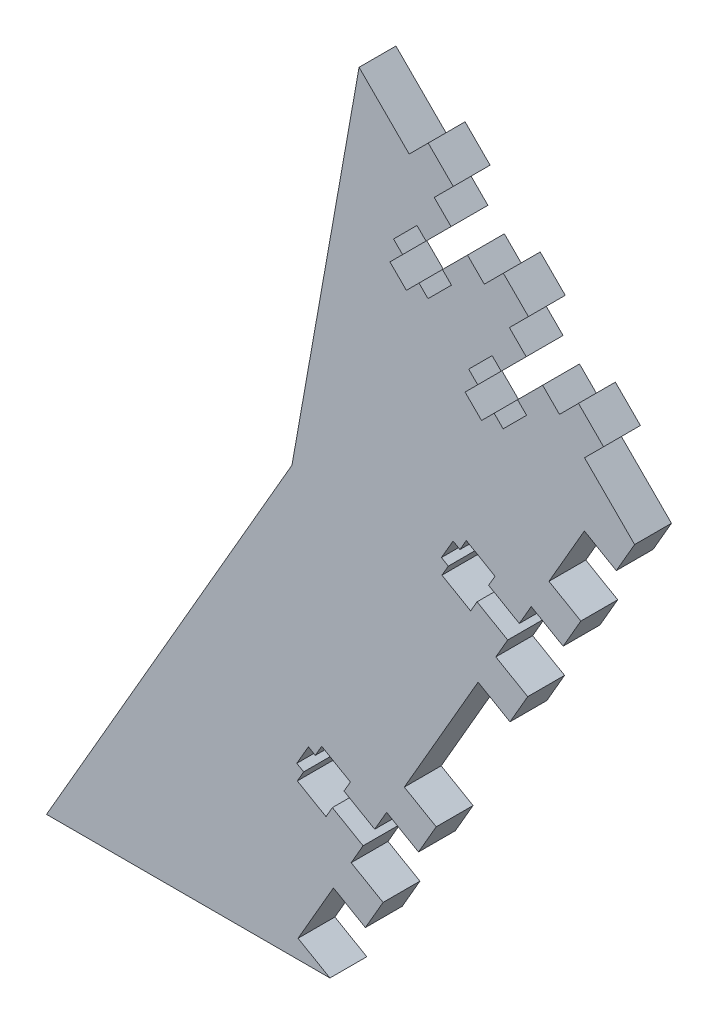
SolidWorks part; units mm, degrees
material "Acrylic (Blue)"
ref_plane "Front Plane" through (0, 0, 0) normal (0, 0, 1) x (1, 0, 0)
ref_plane "Top Plane" through (0, 0, 0) normal (0, 1, 0) x (1, 0, 0)
ref_plane "Right Plane" through (0, 0, 0) normal (1, 0, 0) x (0, 0, -1)
sketch "Sketch1" plane through (0, 0, 0) normal (0, 0, 1) x (1, 0, 0)
  line L0 (0, 0) -> (0, 304.4261) construction
  line L1 (0, 304.4261) -> (215.5261, 88.9)
  line L2 (215.5261, 88.9) -> (164.1997, 0)
  line L3 (164.1997, 0) -> (0, 0)
  line L4 (0, 304.4261) -> (-215.5261, 88.9)
  line L5 (-215.5261, 88.9) -> (-164.1997, 0)
  line L6 (-164.1997, 0) -> (0, 0)
  line L7 (-215.5261, 88.9) -> (215.5261, 88.9) construction
  line L8 (0, 304.4261) -> (3.5921, 308.0182) construction
  line L9 (3.5921, 308.0182) -> (219.1182, 92.4921) construction
  line L10 (219.1182, 92.4921) -> (215.5261, 88.9) construction
  line L11 (3.5921, 308.0182) -> (0, 311.6104) construction
  line L12 (0, 311.6104) -> (-219.1182, 92.4921) construction
  line L13 (-219.1182, 92.4921) -> (-215.5261, 88.9) construction
  line L14 (215.5261, 88.9) -> (219.9256, 86.36) construction
  line L15 (219.9256, 86.36) -> (168.5991, -2.54) construction
  line L16 (168.5991, -2.54) -> (164.1997, 0) construction
  line L17 (164.1997, 0) -> (164.1997, -12.7) construction
  line L18 (164.1997, -12.7) -> (-164.1997, -12.7) construction
  line L19 (-164.1997, -12.7) -> (-164.1997, 0) construction
  line L20 (-164.1997, 0) -> (-168.5991, -2.54) construction
  line L21 (-168.5991, -2.54) -> (-219.9256, 86.36) construction
  line L22 (-219.9256, 86.36) -> (-215.5261, 88.9) construction
  dimension "D1" = 304.8
  dimension "D2" = 120
  dimension "D3" = 88.9
  dimension "D4" = 5.08
  dimension "D5" = 12.7
extrude "Boss-Extrude1" add sketch "Sketch1" along normal blind 6.604
other "Move Face2" face at (107.7631, 196.6631, 3.302) offset 6.35 parameters "D1"=6.35
sketch "Sketch2" plane through (0, 0, 6.604) normal (0, 0, 1) x (1, 0, 0)
  line L1 (113.3997, 0) -> (157.3938, 76.2)
  line L2 (-164.1997, 0) -> (164.1997, 0) construction
  line L3 (157.3938, 76.2) -> (169.4217, 143.9847)
  line L4 (218.8131, 94.5933) -> (4.4901, 308.9163) construction
  line L5 (164.1997, 0) -> (218.8131, 94.5933) construction
  line L7 (169.4217, 143.9847) -> (4.4901, 308.9163)
  line L9 (4.4901, 308.9163) -> (-215.5261, 88.9)
  line L10 (-215.5261, 88.9) -> (-164.1997, 0)
  line L11 (-164.1997, 0) -> (113.3997, 0)
  line B0 (188.424, 103.0706) -> (191.3695, 100.1251) construction
  dimension "D1" = 50.8
  dimension "D2" = 12.7
  dimension "D3" = 76.2
  dimension "D4" = 12.7
sketch_block_instance "NUT_HOLE_2X-1"
sketch_block "NUT_HOLE_2X" parameters "D1"=6.35, "D2"=4.1656, "D3"=25.4, "D4"=4.826, "D5"=8.7376, "D6"=5.9436, "D7"=6.35, "D8"=20.32, "D9"=2
extrude "Cut-Extrude1" cut sketch "Sketch2" against normal through all
sketch "Sketch3" plane through (0, 0, 6.604) normal (0, 0, 1) x (1, 0, 0)
  line L0 (164.1997, 0) -> (218.8131, 94.5933) construction
  line L5 (158.4805, 3.302) -> (209.8069, 92.202)
  line L6 (164.1997, 0) -> (158.4805, 3.302)
  line L7 (215.5261, 88.9) -> (164.1997, 0)
  line L8 (209.8069, 92.202) -> (215.5261, 88.9)
  dimension "D1" = 6.604
  dimension "D2" = 102.6529
extrude "Cut-Extrude2" cut sketch "Sketch3" against normal through all
sketch "Sketch4" plane through (0, 0, 6.604) normal (0, 0, 1) x (1, 0, 0)
  line L0 (218.8131, 94.5933) -> (169.4217, 143.9847) construction
  line L1 (209.8069, 92.202) -> (158.4805, 3.302) construction
  line L2 (215.5261, 88.9) -> (209.8069, 92.202) construction
  point P9 (212.6665, 90.551)
  line B0 (198.1483, 72.0087) -> (192.6491, 75.1837) construction
  line B1 (192.6491, 75.1837) -> (193.7921, 77.1634) construction
  line B2 (193.7921, 77.1634) -> (188.6447, 80.1352) construction
  line B3 (188.6447, 80.1352) -> (187.5017, 78.1555) construction
  line B4 (187.5017, 78.1555) -> (186.2699, 78.8667) construction
  line B5 (186.2699, 78.8667) -> (184.1871, 75.2592) construction
  line B6 (184.1871, 75.2592) -> (185.4189, 74.548) construction
  line B7 (185.4189, 74.548) -> (184.2759, 72.5683) construction
  line B8 (184.2759, 72.5683) -> (189.4233, 69.5965) construction
  line B9 (189.4233, 69.5965) -> (190.5663, 71.5762) construction
  line B10 (190.5663, 71.5762) -> (196.0655, 68.4012) construction
  line B11 (196.0655, 68.4012) -> (193.9319, 64.7057) construction
  line B12 (193.9319, 64.7057) -> (199.6511, 61.4037) construction
  line B13 (199.6511, 61.4037) -> (196.4761, 55.9044) construction
  line B14 (196.4761, 55.9044) -> (190.7569, 59.2064) construction
  line B15 (198.1483, 72.0087) -> (200.2819, 75.7042) construction
  line B16 (200.2819, 75.7042) -> (206.0011, 72.4022) construction
  line B17 (206.0011, 72.4022) -> (209.1761, 77.9015) construction
  line B18 (209.1761, 77.9015) -> (203.4569, 81.2035) construction
  line B19 (196.0655, 68.4012) -> (198.1483, 72.0087) construction
  line B20 (172.2219, 27.1028) -> (166.7226, 30.2778) construction
  line B21 (166.7226, 30.2778) -> (167.8656, 32.2575) construction
  line B22 (167.8656, 32.2575) -> (162.7183, 35.2293) construction
  line B23 (162.7183, 35.2293) -> (161.5753, 33.2496) construction
  line B24 (161.5753, 33.2496) -> (160.3435, 33.9608) construction
  line B25 (160.3435, 33.9608) -> (158.2607, 30.3533) construction
  line B26 (158.2607, 30.3533) -> (159.4925, 29.6421) construction
  line B27 (159.4925, 29.6421) -> (158.3495, 27.6624) construction
  line B28 (158.3495, 27.6624) -> (163.4968, 24.6906) construction
  line B29 (163.4968, 24.6906) -> (164.6398, 26.6703) construction
  line B30 (164.6398, 26.6703) -> (170.1391, 23.4953) construction
  line B31 (170.1391, 23.4953) -> (168.0055, 19.7998) construction
  line B32 (168.0055, 19.7998) -> (173.7247, 16.4978) construction
  line B33 (173.7247, 16.4978) -> (170.5497, 10.9985) construction
  line B34 (170.5497, 10.9985) -> (164.8305, 14.3005) construction
  line B35 (172.2219, 27.1028) -> (174.3555, 30.7983) construction
  line B36 (174.3555, 30.7983) -> (180.0747, 27.4963) construction
  line B37 (180.0747, 27.4963) -> (183.2497, 32.9956) construction
  line B38 (183.2497, 32.9956) -> (177.5305, 36.2976) construction
  line B39 (170.1391, 23.4953) -> (172.2219, 27.1028) construction
  line B40 (185.9095, 127.4969) -> (181.4194, 123.0068) construction
  line B41 (181.4194, 123.0068) -> (179.8029, 124.6232) construction
  line B42 (179.8029, 124.6232) -> (175.6002, 120.4205) construction
  line B43 (175.6002, 120.4205) -> (177.2166, 118.804) construction
  line B44 (177.2166, 118.804) -> (174.9536, 116.541) construction
  line B45 (174.9536, 116.541) -> (177.8991, 113.5955) construction
  line B46 (177.8991, 113.5955) -> (180.1621, 115.8585) construction
  line B47 (180.1621, 115.8585) -> (181.7786, 114.2421) construction
  line B48 (181.7786, 114.2421) -> (185.9813, 118.4448) construction
  line B49 (185.9813, 118.4448) -> (184.3649, 120.0613) construction
  line B50 (184.3649, 120.0613) -> (188.855, 124.5514) construction
  line B51 (188.855, 124.5514) -> (191.8724, 121.534) construction
  line B52 (191.8724, 121.534) -> (195.2849, 124.9465) construction
  line B53 (195.2849, 124.9465) -> (199.775, 120.4564) construction
  line B54 (199.775, 120.4564) -> (196.3625, 117.0439) construction
  line B55 (185.9095, 127.4969) -> (182.8921, 130.5143) construction
  line B56 (182.8921, 130.5143) -> (186.3046, 133.9268) construction
  line B57 (186.3046, 133.9268) -> (181.8145, 138.4169) construction
  line B58 (181.8145, 138.4169) -> (178.402, 135.0044) construction
  line B59 (213.2454, 106.986) -> (209.8329, 103.5735) construction
  line B60 (199.3799, 114.0265) -> (194.8897, 109.5364) construction
  line B61 (194.8897, 109.5364) -> (193.2733, 111.1528) construction
  line B62 (193.2733, 111.1528) -> (189.0705, 106.9501) construction
  line B63 (189.0705, 106.9501) -> (190.687, 105.3336) construction
  line B64 (190.687, 105.3336) -> (188.424, 103.0706) construction
  line B65 (188.424, 103.0706) -> (191.3695, 100.1251) construction
  line B66 (191.3695, 100.1251) -> (193.6325, 102.3881) construction
  line B67 (193.6325, 102.3881) -> (195.249, 100.7717) construction
  line B68 (195.249, 100.7717) -> (199.4517, 104.9744) construction
  line B69 (199.4517, 104.9744) -> (197.8353, 106.5909) construction
  line B70 (197.8353, 106.5909) -> (202.3254, 111.081) construction
  line B71 (202.3254, 111.081) -> (205.3428, 108.0636) construction
  line B72 (205.3428, 108.0636) -> (208.7553, 111.4761) construction
  line B73 (208.7553, 111.4761) -> (213.2454, 106.986) construction
  line B74 (199.3799, 114.0265) -> (196.3625, 117.0439) construction
  line B75 (202.3254, 111.081) -> (199.3799, 114.0265) construction
  dimension "D1" = 12.7
  dimension "D2" = 12.7
  dimension "D3" = 12.7
sketch_block_instance "NUT_HOLE-21"
sketch_block "NUT_HOLE" parameters "D1"=6.35, "D2"=4.1656, "D3"=25.4, "D4"=6.604, "D5"=8.7376, "D6"=5.9436, "D7"=6.35, "D8"=20.32
sketch_block_instance "NUT_HOLE-22"
sketch_block_instance "NUT_HOLE_2X-3"
sketch "Sketch5" plane through (0, 0, 6.604) normal (0, 0, 1) x (1, 0, 0)
  line L0 (185.9095, 127.4969) -> (181.4194, 123.0068) construction
  line L1 (179.8029, 124.6232) -> (175.6002, 120.4205) construction
  line L2 (175.6002, 120.4205) -> (177.2166, 118.804) construction
  line L3 (177.2166, 118.804) -> (174.9536, 116.541) construction
  line L4 (174.9536, 116.541) -> (177.8991, 113.5955) construction
  line L5 (177.8991, 113.5955) -> (180.1621, 115.8585) construction
  line L6 (180.1621, 115.8585) -> (181.7786, 114.2421) construction
  line L7 (181.7786, 114.2421) -> (185.9813, 118.4448) construction
  line L8 (184.3649, 120.0613) -> (188.855, 124.5514) construction
  line L9 (185.9813, 118.4448) -> (184.3649, 120.0613) construction
  line L10 (197.8353, 106.5909) -> (202.3254, 111.081) construction
  line L11 (199.3799, 114.0265) -> (194.8897, 109.5364) construction
  line L12 (194.8897, 109.5364) -> (193.2733, 111.1528) construction
  line L13 (193.2733, 111.1528) -> (189.0705, 106.9501) construction
  line L14 (189.0705, 106.9501) -> (190.687, 105.3336) construction
  line L15 (190.687, 105.3336) -> (188.424, 103.0706) construction
  line L16 (188.424, 103.0706) -> (191.3695, 100.1251) construction
  line L17 (191.3695, 100.1251) -> (193.6325, 102.3881) construction
  line L18 (193.6325, 102.3881) -> (195.249, 100.7717) construction
  line L19 (195.249, 100.7717) -> (199.4517, 104.9744) construction
  line L20 (199.4517, 104.9744) -> (197.8353, 106.5909) construction
  line L21 (185.9095, 127.4969) -> (181.4194, 123.0068)
  line L22 (179.8029, 124.6232) -> (175.6002, 120.4205)
  line L23 (175.6002, 120.4205) -> (177.2166, 118.804)
  line L24 (177.2166, 118.804) -> (174.9536, 116.541)
  line L25 (174.9536, 116.541) -> (177.8991, 113.5955)
  line L26 (177.8991, 113.5955) -> (180.1621, 115.8585)
  line L27 (180.1621, 115.8585) -> (181.7786, 114.2421)
  line L28 (181.7786, 114.2421) -> (185.9813, 118.4448)
  line L29 (184.3649, 120.0613) -> (188.855, 124.5514)
  line L30 (185.9813, 118.4448) -> (184.3649, 120.0613)
  line L31 (197.8353, 106.5909) -> (202.3254, 111.081)
  line L32 (199.3799, 114.0265) -> (194.8897, 109.5364)
  line L33 (194.8897, 109.5364) -> (193.2733, 111.1528)
  line L34 (193.2733, 111.1528) -> (189.0705, 106.9501)
  line L35 (189.0705, 106.9501) -> (190.687, 105.3336)
  line L36 (190.687, 105.3336) -> (188.424, 103.0706)
  line L37 (188.424, 103.0706) -> (191.3695, 100.1251)
  line L38 (191.3695, 100.1251) -> (193.6325, 102.3881)
  line L39 (193.6325, 102.3881) -> (195.249, 100.7717)
  line L40 (195.249, 100.7717) -> (199.4517, 104.9744)
  line L41 (199.4517, 104.9744) -> (197.8353, 106.5909)
  line L42 (181.4194, 123.0068) -> (179.8029, 124.6232) construction
  line L43 (181.4194, 123.0068) -> (179.8029, 124.6232)
  line L44 (198.1483, 72.0087) -> (192.6491, 75.1837) construction
  line L45 (192.6491, 75.1837) -> (193.7921, 77.1634) construction
  line L46 (193.7921, 77.1634) -> (188.6447, 80.1352) construction
  line L47 (188.6447, 80.1352) -> (187.5017, 78.1555) construction
  line L48 (187.5017, 78.1555) -> (186.2699, 78.8667) construction
  line L49 (186.2699, 78.8667) -> (184.1871, 75.2592) construction
  line L50 (184.1871, 75.2592) -> (185.4189, 74.548) construction
  line L51 (185.4189, 74.548) -> (184.2759, 72.5683) construction
  line L52 (184.2759, 72.5683) -> (189.4233, 69.5965) construction
  line L53 (189.4233, 69.5965) -> (190.5663, 71.5762) construction
  line L54 (190.5663, 71.5762) -> (196.0655, 68.4012) construction
  line L55 (172.2219, 27.1028) -> (166.7226, 30.2778) construction
  line L56 (167.8656, 32.2575) -> (162.7183, 35.2293) construction
  line L57 (162.7183, 35.2293) -> (161.5753, 33.2496) construction
  line L58 (161.5753, 33.2496) -> (160.3435, 33.9608) construction
  line L59 (160.3435, 33.9608) -> (158.2607, 30.3533) construction
  line L60 (158.2607, 30.3533) -> (159.4925, 29.6421) construction
  line L61 (159.4925, 29.6421) -> (158.3495, 27.6624) construction
  line L62 (158.3495, 27.6624) -> (163.4968, 24.6906) construction
  line L63 (163.4968, 24.6906) -> (164.6398, 26.6703) construction
  line L64 (164.6398, 26.6703) -> (170.1391, 23.4953) construction
  line L65 (166.7226, 30.2778) -> (167.8656, 32.2575) construction
  line L66 (198.1483, 72.0087) -> (192.6491, 75.1837)
  line L67 (192.6491, 75.1837) -> (193.7921, 77.1634)
  line L68 (193.7921, 77.1634) -> (188.6447, 80.1352)
  line L69 (188.6447, 80.1352) -> (187.5017, 78.1555)
  line L70 (187.5017, 78.1555) -> (186.2699, 78.8667)
  line L71 (186.2699, 78.8667) -> (184.1871, 75.2592)
  line L72 (184.1871, 75.2592) -> (185.4189, 74.548)
  line L73 (185.4189, 74.548) -> (184.2759, 72.5683)
  line L74 (184.2759, 72.5683) -> (189.4233, 69.5965)
  line L75 (189.4233, 69.5965) -> (190.5663, 71.5762)
  line L76 (190.5663, 71.5762) -> (196.0655, 68.4012)
  line L77 (172.2219, 27.1028) -> (166.7226, 30.2778)
  line L78 (167.8656, 32.2575) -> (162.7183, 35.2293)
  line L79 (162.7183, 35.2293) -> (161.5753, 33.2496)
  line L80 (161.5753, 33.2496) -> (160.3435, 33.9608)
  line L81 (160.3435, 33.9608) -> (158.2607, 30.3533)
  line L82 (158.2607, 30.3533) -> (159.4925, 29.6421)
  line L83 (159.4925, 29.6421) -> (158.3495, 27.6624)
  line L84 (158.3495, 27.6624) -> (163.4968, 24.6906)
  line L85 (163.4968, 24.6906) -> (164.6398, 26.6703)
  line L86 (164.6398, 26.6703) -> (170.1391, 23.4953)
  line L87 (166.7226, 30.2778) -> (167.8656, 32.2575)
  line L88 (170.1391, 23.4953) -> (172.2219, 27.1028)
  line L89 (198.1483, 72.0087) -> (196.0655, 68.4012)
  line L90 (185.9095, 127.4969) -> (188.855, 124.5514)
  line L91 (199.3799, 114.0265) -> (202.3254, 111.081)
  point P0 (179.8029, 124.6232)
extrude "Cut-Extrude3" cut sketch "Sketch5" against normal through all
sketch "Sketch6" plane through (0, 0, 6.604) normal (0, 0, 1) x (1, 0, 0)
  line L0 (181.8145, 138.4169) -> (178.402, 135.0044) construction
  line L1 (182.8921, 130.5143) -> (186.3046, 133.9268) construction
  line L2 (186.3046, 133.9268) -> (181.8145, 138.4169) construction
  line L3 (191.8724, 121.534) -> (195.2849, 124.9465) construction
  line L4 (195.2849, 124.9465) -> (199.775, 120.4564) construction
  line L5 (199.775, 120.4564) -> (196.3625, 117.0439) construction
  line L6 (208.7553, 111.4761) -> (213.2454, 106.986) construction
  line L7 (205.3428, 108.0636) -> (208.7553, 111.4761) construction
  line L8 (213.2454, 106.986) -> (209.8329, 103.5735) construction
  line L9 (181.8145, 138.4169) -> (178.402, 135.0044)
  line L10 (182.8921, 130.5143) -> (186.3046, 133.9268)
  line L11 (186.3046, 133.9268) -> (181.8145, 138.4169)
  line L12 (191.8724, 121.534) -> (195.2849, 124.9465)
  line L13 (195.2849, 124.9465) -> (199.775, 120.4564)
  line L14 (199.775, 120.4564) -> (196.3625, 117.0439)
  line L15 (208.7553, 111.4761) -> (213.2454, 106.986)
  line L16 (205.3428, 108.0636) -> (208.7553, 111.4761)
  line L17 (213.2454, 106.986) -> (209.8329, 103.5735)
  line L27 (209.1761, 77.9015) -> (203.4569, 81.2035) construction
  line L28 (206.0011, 72.4022) -> (209.1761, 77.9015) construction
  line L29 (200.2819, 75.7042) -> (206.0011, 72.4022) construction
  line L30 (193.9319, 64.7057) -> (199.6511, 61.4037) construction
  line L31 (199.6511, 61.4037) -> (196.4761, 55.9044) construction
  line L32 (196.4761, 55.9044) -> (190.7569, 59.2064) construction
  line L33 (183.2497, 32.9956) -> (177.5305, 36.2976) construction
  line L34 (180.0747, 27.4963) -> (183.2497, 32.9956) construction
  line L35 (174.3555, 30.7983) -> (180.0747, 27.4963) construction
  line L36 (168.0055, 19.7998) -> (173.7247, 16.4978) construction
  line L37 (173.7247, 16.4978) -> (170.5497, 10.9985) construction
  line L38 (170.5497, 10.9985) -> (164.8305, 14.3005) construction
  line L39 (209.1761, 77.9015) -> (203.4569, 81.2035)
  line L40 (206.0011, 72.4022) -> (209.1761, 77.9015)
  line L41 (200.2819, 75.7042) -> (206.0011, 72.4022)
  line L42 (178.402, 135.0044) -> (182.8921, 130.5143)
  line L43 (191.8724, 121.534) -> (196.3625, 117.0439)
  line L44 (205.3428, 108.0636) -> (209.8329, 103.5735)
  line L45 (203.4569, 81.2035) -> (200.2819, 75.7042)
  line L46 (193.9319, 64.7057) -> (199.6511, 61.4037)
  line L47 (199.6511, 61.4037) -> (196.4761, 55.9044)
  line L48 (196.4761, 55.9044) -> (190.7569, 59.2064)
  line L49 (183.2497, 32.9956) -> (177.5305, 36.2976)
  line L50 (180.0747, 27.4963) -> (183.2497, 32.9956)
  line L51 (174.3555, 30.7983) -> (180.0747, 27.4963)
  line L52 (168.0055, 19.7998) -> (173.7247, 16.4978)
  line L53 (173.7247, 16.4978) -> (170.5497, 10.9985)
  line L54 (170.5497, 10.9985) -> (164.8305, 14.3005)
  line L55 (164.8305, 14.3005) -> (168.0055, 19.7998)
  line L56 (174.3555, 30.7983) -> (177.5305, 36.2976)
  line L57 (190.7569, 59.2064) -> (193.9319, 64.7057)
extrude "Boss-Extrude2" add sketch "Sketch6" against normal up to surface (6.604 mm away) up to face at (181.4168, 79.6586, 0)
other "Move Face3" [suppressed] offset 0.0508 parameters "D1"=0.0508
